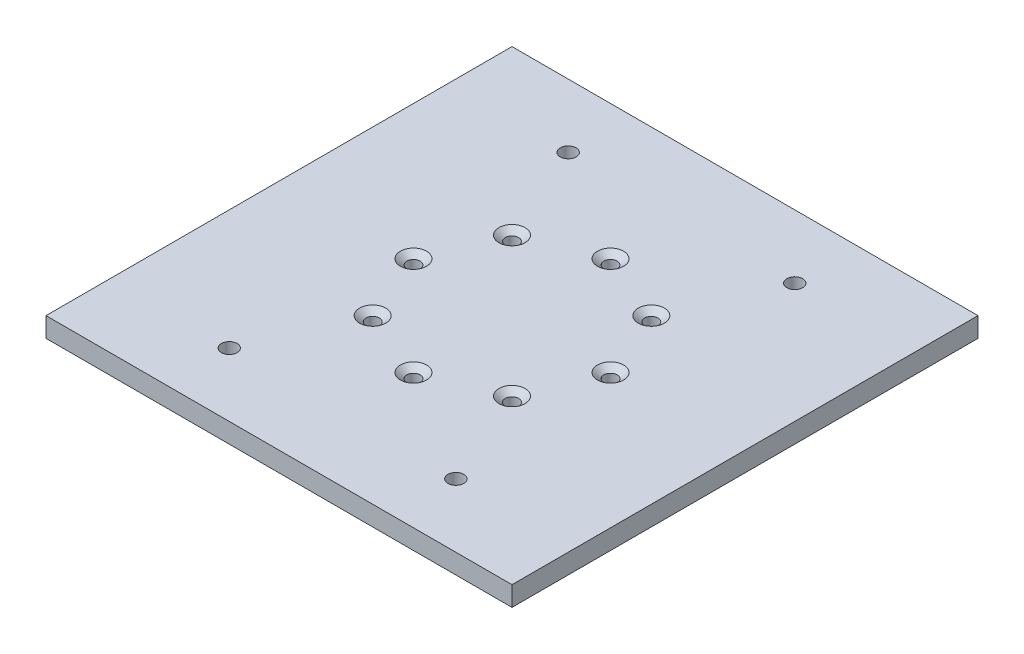
SolidWorks part; units mm, degrees
material "6061-T6 (SS)"
ref_plane "Front Plane" through (0, 0, 0) normal (0, 0, 1) x (1, 0, 0)
ref_plane "Top Plane" through (0, 0, 0) normal (0, 1, 0) x (1, 0, 0)
ref_plane "Right Plane" through (0, 0, 0) normal (1, 0, 0) x (0, 0, -1)
sketch "Sketch1" plane through (0, 0, 0) normal (0, 1, 0) x (1, 0, 0)
  line L1 (-75.0888, -75.0888) -> (75.0888, -75.0888)
  line L2 (-75.0888, -75.0888) -> (-75.0888, 75.0888)
  line L3 (-75.0888, 75.0888) -> (75.0888, 75.0888)
  line L4 (75.0888, -75.0888) -> (75.0888, 75.0888)
  line L10 (-75.0888, 75.0888) -> (0, 0) construction
  line L11 (-38.1, 73.025) -> (38.1, 73.025) construction
  line L12 (-38.1, 73.025) -> (-38.1, 47.625) construction
  line L13 (-38.1, 47.625) -> (38.1, 47.625) construction
  line L14 (38.1, 73.025) -> (38.1, 47.625) construction
  line L15 (-38.1, 73.025) -> (38.1, 47.625) construction
  line L16 (-38.1, 47.625) -> (38.1, 73.025) construction
  line L17 (-44.45, 75.565) -> (44.45, 75.565) construction
  line L18 (-44.45, 75.565) -> (-44.45, 45.085) construction
  line L19 (-44.45, 45.085) -> (44.45, 45.085) construction
  line L20 (44.45, 75.565) -> (44.45, 45.085) construction
  line L21 (-44.45, 75.565) -> (44.45, 45.085) construction
  line L22 (-44.45, 45.085) -> (44.45, 75.565) construction
  line L23 (0, 0) -> (75.0888, 75.0888) construction
  line L24 (0, 0) -> (-75.0888, -75.0888) construction
  line L25 (0, 0) -> (75.0888, -75.0888) construction
  circle A0 centre (0, 0) radius 38.1 construction
  circle A1 centre (0, 0) radius 41.275 construction
  point P0 (0, 0)
  point P17 (0, 60.325)
  point P22 (0, 60.325)
  point P27 (-75.0888, 0)
  point P28 (0, 75.565)
  dimension "D4" = 76.2
  dimension "D5" = 82.55
  dimension "D6" = 2.54
  dimension "D7" = 25.4
  dimension "D8" = 76.2
  dimension "D9" = 88.9
  dimension "D10" = 6.35
  dimension "D12" = 150.1775
extrude "Boss-Extrude1" add sketch "Sketch1" along normal blind 6.35
hole_wizard "#7 (0.201) Diameter Hole1" positions "Sketch3" profile "Sketch2" hole size "#7" standard "ANSI Inch" end condition through all
sketch "Sketch3" plane through (0, 6.35, 0) normal (0, 1, 0) x (-1, 0, 0)
  line L0 (-36.5125, -54.61) -> (0, 0) construction
  line L1 (0, 0) -> (36.5125, -54.61) construction
  line L5 (-873.478, -47.625) -> (49126.522, -47.625) construction
  point P0 (36.5125, -54.61)
  point P1 (-36.5125, -54.61)
  dimension "D1" = 73.025
  dimension "D2" = 47.625
  dimension "D3" = 6.985
sketch "Sketch2" plane through (-36.5125, 6.35, -54.61) normal (1, 0, 0) x (0, 0, 1)
  line L0 (0, 0) -> (0, 6.35)
  line L1 (0, 6.35) -> (2.5527, 6.35)
  line L2 (2.5527, 6.35) -> (2.5527, 0)
  line L5 (2.5527, 0) -> (0, 0)
  line L11 (0, -6.35) -> (0, 107.95) construction
  dimension "Thru Hole Dia." = 5.1054
  dimension "Thru Hole Depth" = 6.35
ref_axis "Axis1" through (0, 0, 0) along (0, 1, 0)
pattern_circular "CirPattern1" count 2 over 360 about axis through (0, 0, 0) along (0, 1, 0) of "#7 (0.201) Diameter Hole1"
hole_wizard "CSK for #8 Flat Head Machine Screw (100)1" positions "Sketch5" profile "Sketch4" countersink size "#8" standard "Ansi Inch" end condition through all
sketch "Sketch5" plane through (0, 6.35, 0) normal (0, 1, 0) x (-1, 0, 0)
  point P0 (0, 31.75)
  dimension "D1" = 31.75
sketch "Sketch4" plane through (0, 6.35, 31.75) normal (1, 0, 0) x (0, 0, 1)
  line L0 (0, 0) -> (0, 6.35)
  line L1 (0, 6.35) -> (2.1526, 6.35)
  line L2 (2.1526, 6.35) -> (2.1526, 1.7317)
  line L3 (2.1526, 1.7317) -> (4.2164, 0)
  line L5 (4.2164, 0) -> (0, 0)
  line L6 (-2.1526, 1.7317) -> (-4.2164, 0) construction
  line L11 (0, -6.35) -> (0, 107.95) construction
  dimension "Thru Hole Dia." = 4.3053
  dimension "Thru Hole Depth" = 6.35
  dimension "Near C'Sink Dia." = 8.4328
  dimension "Near C'Sink Angle" = 100
pattern_circular "CirPattern2" count 8 over 360 about axis through (0, 0, 0) along (0, 1, 0) of "CSK for #8 Flat Head Machine Screw (100)1"
